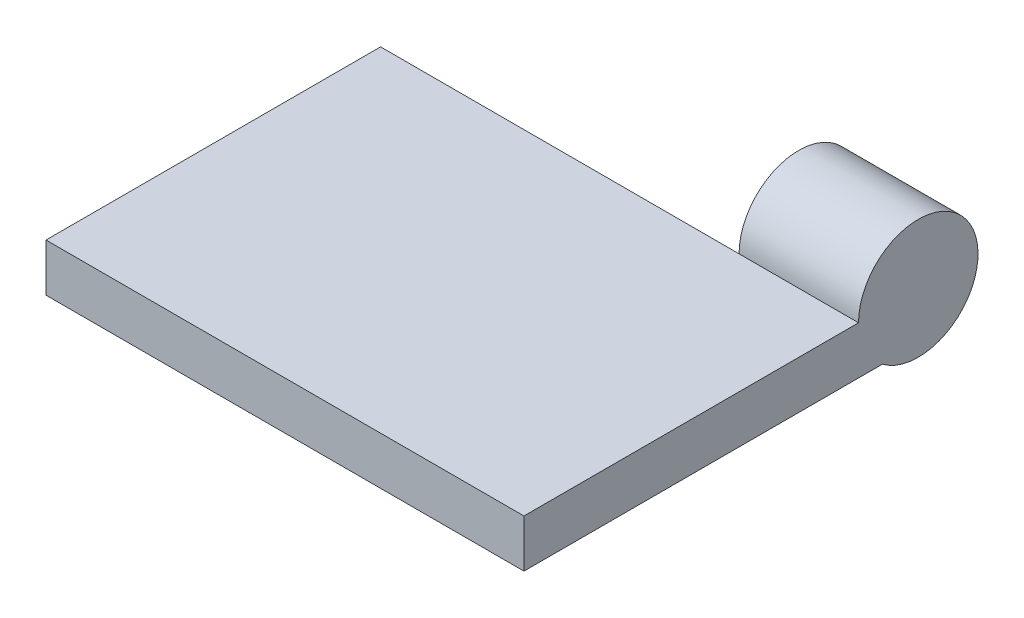
SolidWorks part; units mm, degrees
ref_plane "Front Plane" through (0, 0, 0) normal (0, 0, 1) x (1, 0, 0)
ref_plane "Top Plane" through (0, 0, 0) normal (0, 1, 0) x (1, 0, 0)
ref_plane "Right Plane" through (0, 0, 0) normal (1, 0, 0) x (0, 0, -1)
sketch "Sketch2" plane through (0, 0, 0) normal (0, 1, 0) x (1, 0, 0)
  line L1 (-10, -7) -> (10, -7)
  line L2 (-10, -7) -> (-10, 7)
  line L3 (-10, 7) -> (10, 7)
  line L4 (10, -7) -> (10, 7)
  line L5 (-10, -7) -> (10, 7) construction
  line L6 (-10, 7) -> (10, -7) construction
  point P0 (0, 0)
  dimension "D1" = 14
  dimension "D2" = 20
extrude "Boss-Extrude2" add sketch "Sketch2" along normal blind 2
sketch "Sketch3" plane through (10, 0, 0) normal (1, 0, 0) x (0, 0, -1)
  line L0 (7, 2) -> (12, 2)
  line L1 (7, 0) -> (8, 0)
  arc A0 (8, 0) -> (7, 2) centre (9.5, 2) ccw
  line M2 (7, 0) -> (7, 2)
  dimension "D1" = 5
extrude "Boss-Extrude3" add sketch "Sketch3" against normal blind 5 contours L1 A0 L0 M2 | L0 A0 region at (10, 3.061, -9.5) region at (10, 0.9123, -9.372)
ref_plane "Plane1" through (2.5, 0, 0) normal (-1, 0, 0) x (0, 0, 1)
